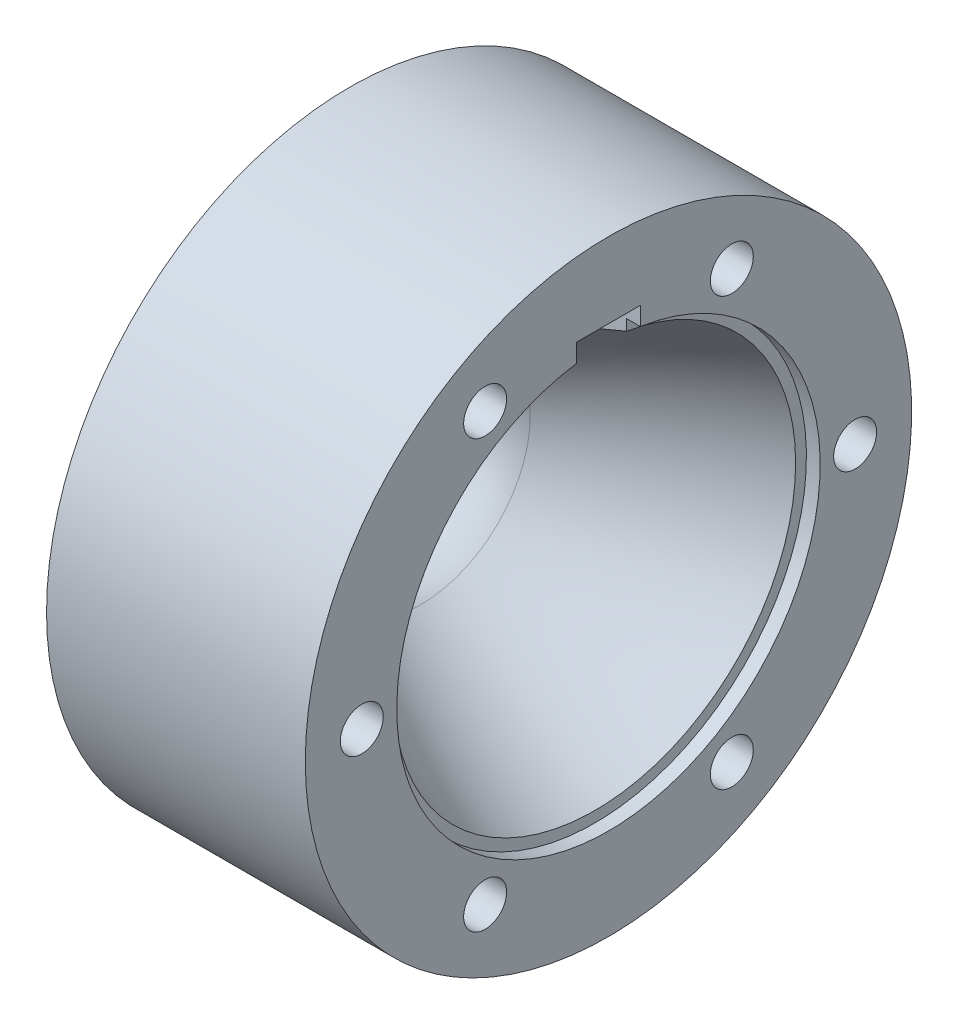
SolidWorks part; units mm, degrees
material "6061-T6 (SS)"
ref_plane "Front Plane" through (0, 0, 0) normal (0, 0, 1) x (1, 0, 0)
ref_plane "Top Plane" through (0, 0, 0) normal (0, 1, 0) x (1, 0, 0)
ref_plane "Right Plane" through (0, 0, 0) normal (1, 0, 0) x (0, 0, -1)
sketch "Sketch1" plane through (0, 0, 0) normal (0, 0, 1) x (1, 0, 0)
  line L0 (0, 0) -> (0, 5)
  line L1 (0, 5) -> (13.4959, 12.623)
  line L2 (0, 0) -> (5.704, 0) construction
  line L3 (13.4959, 12.623) -> (13.4959, 13.303)
  line L4 (13.4959, 13.303) -> (14.359, 13.303)
  line L5 (14.359, 13.303) -> (14.359, 19.05)
  line L6 (14.359, 19.05) -> (-0.75, 19.05)
  line L7 (-0.75, 19.05) -> (-0.75, 0)
  line L9 (1.7704, 6) -> (1.7704, 6.3023)
  line L10 (1.7704, 6) -> (-0.75, 6)
  line L11 (1.7704, 6) -> (1.7704, 0)
  line L13 (-0.75, 6) -> (-0.75, 0)
  arc A0 (0, 5) -> (13.4959, 12.623) centre (33.8316, -39.1379) cw
  dimension "D1" = 5
  dimension "D2" = 13.303
  dimension "D3" = 15.5
  dimension "D4" = 0.8631
  dimension "D5" = 0.68
  dimension "D6" = 6
  dimension "D7" = 0.75
  dimension "D8" = 19.05
  dimension "D9" = 15.109
revolve "Revolve1" add sketch "Sketch1" angle 360 about L2 region at (5.7591, 13.9163, 0)
sketch "Sketch2" plane through (14.359, 0, 0) normal (1, 0, 0) x (0, 0, -1)
  line L1 (-2, 13.303) -> (2, 13.303)
  line L2 (-2, 14.303) -> (2, 14.303)
  line L3 (-2, 14.303) -> (-2, 12.303)
  line L4 (-2, 12.303) -> (2, 12.303)
  line L5 (2, 14.303) -> (2, 12.303)
  line L6 (-2, 14.303) -> (2, 12.303) construction
  line L7 (-2, 12.303) -> (2, 14.303) construction
  line L8 (-2, 12.303) -> (2, 12.303)
  line L9 (-2, 12.303) -> (-2, 6.6634)
  line L10 (-2, 6.6634) -> (2, 6.6634)
  line L11 (2, 12.303) -> (2, 6.6634)
  circle A0 centre (0, 0) radius 19.05 construction
  circle A1 centre (0, 0) radius 13.303 construction
  circle A2 centre (0, 0) radius 19.05
  circle A3 centre (0, 0) radius 13.303
  point P1 (0, 13.303)
  circle M10 centre (0, 0) radius 13.303
  dimension "D1" = 4
  dimension "D2" = 2
extrude "Cut-Extrude1" cut sketch "Sketch2" against normal blind 4.2 contours L5 L3 L4 M10 | L1 L3 M10 | L5 L1 M10 | L11 L4 L9 L10 | L5 L2 L3 L1 region at (14.359, 13.803, 0) region at (14.359, 13.2577, 1.5006) region at (14.359, 13.2577, -1.5006) region at (14.359, 12.7789, 0) region at (14.359, 9.4832, 0)
sketch "Sketch3" plane through (-0.75, 0, 0) normal (-1, 0, 0) x (0, 0, 1)
  line L0 (8, 6) -> (9.4125, 6) construction
  line L1 (8, -8) -> (-8, -8)
  line L2 (8, -8) -> (8, 8)
  line L3 (8, 8) -> (-8, 8)
  line L4 (-8, -8) -> (-8, 8)
  line L5 (8, -8) -> (-8, 8) construction
  line L6 (8, 8) -> (-8, -8) construction
  line L7 (8, 7.5875) -> (9.4125, 7.5875)
  line L8 (8, 4.4125) -> (9.4125, 4.4125)
  line L9 (-8, -6) -> (-9.4125, -6) construction
  line L10 (-8, -7.5875) -> (-9.4125, -7.5875)
  line L11 (-8, -4.4125) -> (-9.4125, -4.4125)
  line L12 (-8.7063, -6) -> (-8.7062, 0) construction
  line L13 (8.7063, 6) -> (8.7063, 0) construction
  line L14 (-11, -5.9429) -> (-11, 1.6841) construction
  line L15 (11, 6) -> (11, -1.6351) construction
  circle A0 centre (-8, 8) radius 1.5875
  circle A1 centre (0, 0) radius 19.05
  circle A2 centre (0, 0) radius 19.05
  circle A3 centre (8, 8) radius 1.5875
  circle A4 centre (8, -8) radius 1.5875
  circle A5 centre (-8, -8) radius 1.5875
  arc A6 (8, 7.5875) -> (8, 4.4125) centre (8, 6) ccw
  arc A7 (9.4125, 4.4125) -> (9.4125, 7.5875) centre (9.4125, 6) ccw
  arc A8 (-8, -7.5875) -> (-8, -4.4125) centre (-8, -6) ccw
  arc A9 (-9.4125, -4.4125) -> (-9.4125, -7.5875) centre (-9.4125, -6) ccw
  circle A10 centre (-9.4125, -7.5875) radius 3.175
  circle A11 centre (9.4125, 7.5875) radius 3.175
  point P9 (8.7063, 6)
  point P18 (-8.7063, -6)
  circle M11 centre (0, 0) radius 19.05
  dimension "D2" = 3.175
  dimension "D3" = 16
  dimension "D4" = 2
  dimension "D5" = 3.175
  dimension "D6" = 19
  dimension "D7" = 19
  dimension "D1" = 0
extrude "Boss-Extrude1" add sketch "Sketch3" along normal blind 1.15 contours A5 L4 A0 L3 A3 L2 A4 L1 M11 region at (-0.75, 0, -18.5112)
sketch "Sketch5" plane through (14.359, 0, 0) normal (1, 0, 0) x (0, 0, -1)
  line L0 (0, 0) -> (-15.5, 0) construction
  circle A0 centre (-15.5, 0) radius 1.35
  circle A1 centre (-7.75, 13.4234) radius 1.35
  circle A2 centre (7.75, 13.4234) radius 1.35
  circle A8 centre (0, 0) radius 15.5 construction
  circle A9 centre (15.5, 0) radius 1.35
  circle A10 centre (7.75, -13.4234) radius 1.35
  circle A11 centre (-7.75, -13.4234) radius 1.35
  dimension "D1" = 2.7
  dimension "D3" = 31
  dimension "D2" = 6
extrude "Cut-Extrude4" cut sketch "Sketch5" against normal up to surface (16.259 mm away) contours A0 | A0 | A11 | A10 | A9 | A2 | A1 region at (14.359, 0, 15.5) region at (14.359, 13.4234, 7.75) region at (14.359, 13.4234, -7.75) region at (14.359, 0, -15.5) region at (14.359, -13.4234, -7.75) region at (14.359, -13.4234, 7.75) up to face at (-1.9, 0, 0)
fillet "Fillet1" radius 5 8 edges at (-1.325, 8, -6.4125) (-1.325, 6.4125, -8) (-1.325, -4.4125, -8) (-1.325, 4.4125, 8) (-1.325, -6.4125, 8) (-1.325, -8, 6.4125) (-1.325, 8, 6.2644) (-1.325, -8, -6.2644)
sketch "Sketch6" plane through (-1.9, 0, 0) normal (-1, 0, 0) x (0, 0, 1)
  circle A0 centre (0, 0) radius 19.05 construction
  circle A1 centre (0, 0) radius 19.05
  circle A2 centre (-11.2583, 6.5) radius 1.4958
  circle A3 centre (0, 13) radius 1.4958
  circle A4 centre (11.2583, -6.5) radius 1.4958
  circle A5 centre (0, -13) radius 1.4958
  circle A6 centre (0, 0) radius 13 construction
  dimension "D1" = 26
  dimension "D2" = 60
extrude "Cut-Extrude5" cut sketch "Sketch6" against normal blind 10 contours A2 | A3 | A4 | A5 region at (-1.9, 6.5, -11.2583) region at (-1.9, 13, 0) region at (-1.9, -6.5, 11.2583) region at (-1.9, -13, 0)
sketch "Sketch7" plane through (-0.75, 0, 0) normal (-1, 0, 0) x (0, 0, 1)
  line L1 (8, 8) -> (-8, 8) construction
  line L2 (8, 8) -> (8, -8) construction
  line L3 (8, -8) -> (-8, -8) construction
  line L4 (-8, 3.711) -> (-8, -0.2417)
  line L5 (-3.2859, -8) -> (3.711, -8)
  line L6 (8, -3.711) -> (8, 0.2417)
  line L7 (3.2859, 8) -> (-3.711, 8)
  line L8 (-8, 3.711) -> (-8, -0.2417)
  line L9 (-3.2859, -8) -> (3.711, -8)
  line L10 (8, -3.711) -> (8, 0.2417)
  line L11 (3.2859, 8) -> (-3.711, 8)
  line L12 (-8, 8) -> (-8, -8) construction
  line L13 (8, 8) -> (-8, -8) construction
  line L14 (8, -8) -> (-8, 8) construction
  line L19 (0, 0) -> (0, 5.4353) construction
  arc A4 (-9.8827, -4.151) -> (-6.2249, -8.955) centre (-8, -6.512) cw
  arc A7 (6.2249, 8.955) -> (9.8827, 4.151) centre (8, 6.512) ccw
  circle A9 centre (0, 0) radius 6 construction
  circle A10 centre (0, 0) radius 6
  arc A16 (-10.8058, -4.7346) -> (-8, -0.2417) centre (-13, -0.2417) ccw
  arc A17 (10.8058, 4.7346) -> (7.033, 9.6896) centre (9.4125, 7.5875) ccw
  arc A18 (10.8058, 4.7346) -> (7.033, 9.6896) centre (9.4125, 7.5875) ccw
  arc A19 (-10.8058, -4.7346) -> (-7.033, -9.6896) centre (-9.4125, -7.5875) ccw
  arc A20 (-10.8058, -4.7346) -> (-7.033, -9.6896) centre (-9.4125, -7.5875) ccw
  arc A21 (6.9664, -9.2049) -> (3.711, -8) centre (3.711, -13) ccw
  arc A22 (6.9664, -9.2049) -> (9.2049, -6.9664) centre (8, -8) ccw
  arc A23 (8, -3.711) -> (9.2049, -6.9664) centre (13, -3.711) ccw
  arc A24 (10.8058, 4.7346) -> (8, 0.2417) centre (13, 0.2417) ccw
  arc A29 (-6.9664, 9.2049) -> (-3.711, 8) centre (-3.711, 13) ccw
  arc A30 (-6.9664, 9.2049) -> (-9.2049, 6.9664) centre (-8, 8) ccw
  arc A31 (-8, 3.711) -> (-9.2049, 6.9664) centre (-13, 3.711) ccw
  arc A32 (-10.8058, -4.7346) -> (-8, -0.2417) centre (-13, -0.2417) ccw
  arc A37 (6.9664, -9.2049) -> (3.711, -8) centre (3.711, -13) ccw
  arc A38 (6.9664, -9.2049) -> (9.2049, -6.9664) centre (8, -8) ccw
  arc A39 (8, -3.711) -> (9.2049, -6.9664) centre (13, -3.711) ccw
  arc A40 (10.8058, 4.7346) -> (8, 0.2417) centre (13, 0.2417) ccw
  arc A45 (-6.9664, 9.2049) -> (-3.711, 8) centre (-3.711, 13) ccw
  arc A46 (-6.9664, 9.2049) -> (-9.2049, 6.9664) centre (-8, 8) ccw
  arc A47 (-8, 3.711) -> (-9.2049, 6.9664) centre (-13, 3.711) ccw
  arc A51 (3.2859, 8) -> (7.033, 9.6896) centre (3.2859, 13) ccw
  arc A52 (3.2859, 8) -> (7.033, 9.6896) centre (3.2859, 13) ccw
  arc A53 (-3.2859, -8) -> (-7.033, -9.6896) centre (-3.2859, -13) ccw
  arc A54 (-3.2859, -8) -> (-7.033, -9.6896) centre (-3.2859, -13) ccw
  point P2 (0, 0)
  arc M31 (-8, -0.2417) -> (-10.8058, -4.7346) centre (-13, -0.2417) cw
  arc M41 (8, 0.2417) -> (10.8058, 4.7346) centre (13, 0.2417) cw
  circle M50 centre (0, 0) radius 6
  arc M96 (10.8058, 4.7346) -> (7.033, 9.6896) centre (9.4125, 7.5875) ccw
  arc M97 (-10.8058, -4.7346) -> (-7.033, -9.6896) centre (-9.4125, -7.5875) ccw
  arc M102 (7.033, 9.6896) -> (3.2859, 8) centre (3.2859, 13) cw
  arc M103 (-7.033, -9.6896) -> (-3.2859, -8) centre (-3.2859, -13) cw
  dimension "D1" = 0
extrude "Cut-Extrude6" cut sketch "Sketch7" against normal blind 3 contours A4 M31 M97 M103 M50 | A7 M102 M50 M41 M96 region at (-0.75, -7.1149, -8.7919) region at (-0.75, 7.1149, 8.7919)
fillet "Fillet2" radius 5 1 edges at (1.3462, 0, 6)
sketch "Sketch8" plane through (-1.9, 0, 0) normal (-1, 0, 0) x (0, 0, 1)
  line L0 (-5.5974, -4.6827) -> (5.5974, 4.6827)
  circle A0 centre (0, 0) radius 15.2649
  arc A1 (-6.2249, -8.955) -> (-9.8827, -4.151) centre (-8, -6.512) ccw construction
  arc A2 (6.2249, 8.955) -> (9.8827, 4.151) centre (8, 6.512) ccw construction
